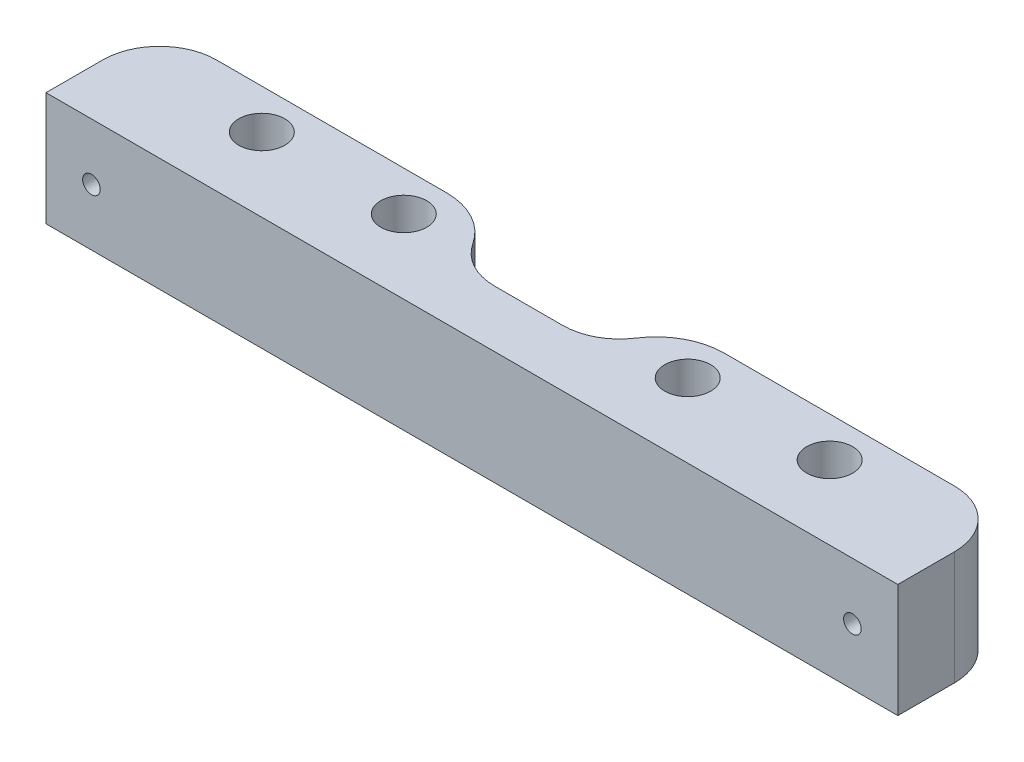
SolidWorks part; units mm, degrees
ref_plane "Front Plane" through (0, 0, 0) normal (0, 0, 1) x (1, 0, 0)
ref_plane "Top Plane" through (0, 0, 0) normal (0, 1, 0) x (1, 0, 0)
ref_plane "Right Plane" through (0, 0, 0) normal (1, 0, 0) x (0, 0, -1)
sketch "Sketch1" plane through (0, 0, 0) normal (0, 1, 0) x (1, 0, 0)
  line L1 (-75, 10) -> (75, 10)
  line L2 (-75, 10) -> (-75, -10)
  line L3 (-75, -10) -> (75, -10)
  line L4 (75, 10) -> (75, -10)
  line L5 (-75, 10) -> (75, -10) construction
  line L6 (-75, -10) -> (75, 10) construction
  circle A0 centre (-25, 3) radius 4.05
  circle A1 centre (25, 3) radius 4.05
  circle A2 centre (-50, 3) radius 4.05
  circle A3 centre (50, 3) radius 4.05
  point P4 (0, 0)
  dimension "D1" = 8.1
  dimension "D2" = 50
  dimension "D3" = 25
  dimension "D4" = 20
  dimension "D5" = 13
  dimension "D6" = 150
  dimension "D7" = 25
  dimension "D8" = 25
extrude "Boss-Extrude1" add sketch "Sketch1" along normal blind 20
fillet "Fillet1" radius 10 2 edges at (75, 10, -10) (-75, 10, -10)
sketch "Sketch3" plane through (0, 0, -10) normal (0, 0, -1) x (-1, 0, 0)
  line L2 (-65, 20) -> (-65, 0) construction
  line L3 (65, 0) -> (65, 20) construction
  line L4 (-65, 20) -> (-75, 20) construction
  circle A0 centre (-67, 10) radius 1.55
  circle A1 centre (67, 10) radius 1.55
  circle A2 centre (-67, 10) radius 3.5
  circle A3 centre (67, 10) radius 3.5
  dimension "D1" = 3.1
  dimension "D2" = 2
  dimension "D5" = 7
  dimension "D3" = 2
  dimension "D4" = 10
extrude "Cut-Extrude1" cut sketch "Sketch3" against normal through all contours A0 | A1 region at (67, 10, -10) region at (-67, 10, -10)
extrude "Cut-Extrude2" cut sketch "Sketch3<3>" against normal blind 3
sketch "Sketch3<3>" plane through (0, 0, -10) normal (0, 0, -1) x (-1, 0, 0) same geometry as "Sketch3"
sketch "Sketch4" plane through (0, 20, 0) normal (0, 1, 0) x (1, 0, 0)
  line L0 (-6, 10) -> (6, 10) construction
  line L1 (65, 10) -> (-65, 10) construction
  line L2 (-6, 20) -> (6, 20)
  line L3 (-6, 0) -> (6, 0)
  arc A0 (-6, 20) -> (-6, 0) centre (-6, 10) ccw
  arc A1 (6, 0) -> (6, 20) centre (6, 10) ccw
  point P4 (0, 10)
  dimension "D2" = 12
  dimension "D1" = 20
extrude "Cut-Extrude3" cut sketch "Sketch4" against normal through all
fillet "Fillet2" radius 12 2 edges at (16, 10, -10) (-16, 10, -10)
